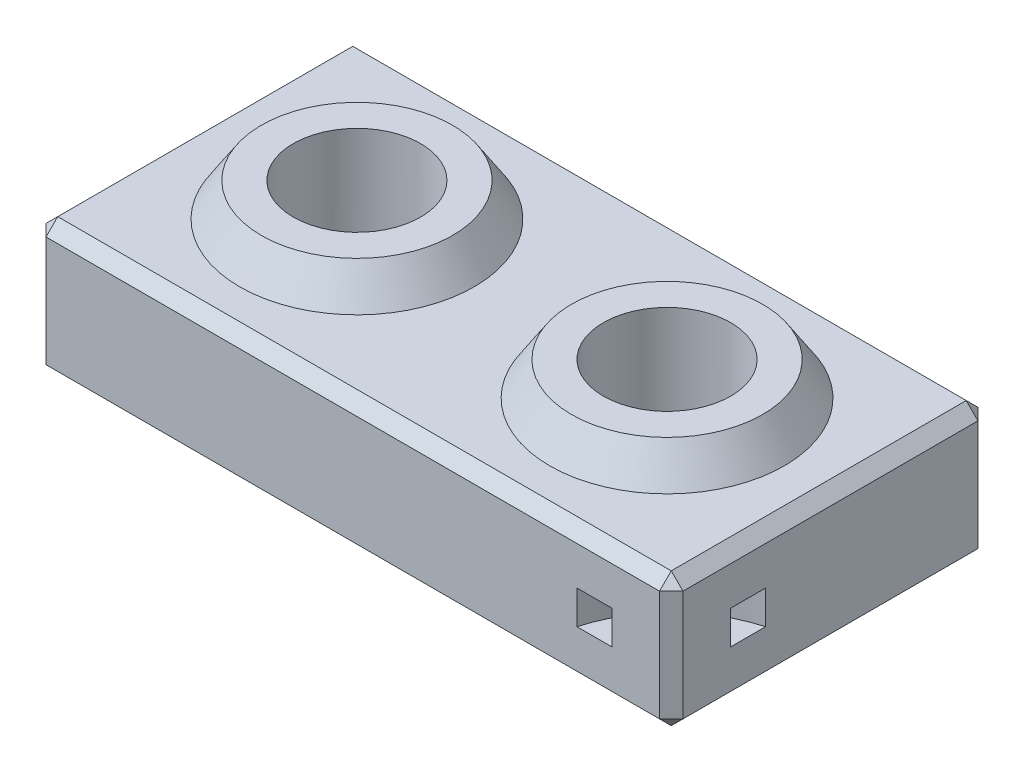
SolidWorks part; units mm, degrees
ref_plane "Alzado" through (0, 0, 0) normal (0, 0, 1) x (1, 0, 0)
ref_plane "Planta" through (0, 0, 0) normal (0, 1, 0) x (1, 0, 0)
ref_plane "Vista lateral" through (0, 0, 0) normal (1, 0, 0) x (0, 0, -1)
sketch "Croquis1" plane through (0, 0, 0) normal (0, 1, 0) x (1, 0, 0)
  line L1 (-19, 9.5) -> (19, 9.5)
  line L2 (-19, 9.5) -> (-19, -9.5)
  line L3 (-19, -9.5) -> (19, -9.5)
  line L4 (19, 9.5) -> (19, -9.5)
  line L5 (-19, 9.5) -> (19, -9.5) construction
  line L6 (-19, -9.5) -> (19, 9.5) construction
  point P0 (0, 0)
  dimension "D1" = 38
  dimension "D2" = 19
extrude "Saliente-Extruir1" add sketch "Croquis1" along normal blind 8
sketch "Croquis2" plane through (0, 8, 0) normal (0, 1, 0) x (1, 0, 0)
  line L0 (-9.25, 0) -> (9.25, 0) construction
  circle A0 centre (-9.25, 0) radius 5
  circle A1 centre (9.25, 0) radius 5
  point P4 (0, 0)
  dimension "D1" = 10
  dimension "D2" = 18.5
extrude "Saliente-Extruir2" add sketch "Croquis2" along normal blind 2
sketch "Croquis3" plane through (0, 10, 0) normal (0, 1, 0) x (1, 0, 0)
  circle A0 centre (9.25, 0) radius 3.8
  circle A1 centre (-9.25, 0) radius 3.8
  circle A2 centre (-9.25, 0) radius 5 construction
  dimension "D1" = 1.2
extrude "Cortar-Extruir1" cut sketch "Croquis3" against normal through all
chamfer "Chaflán2" distance 0.7 angle 45 12 edges at (19, 8, 0) (19, 0, 0) (19, 4, -9.5) (0, 8, -9.5) (0, 0, -9.5) (-19, 4, -9.5) (-19, 8, 0) (-19, 0, 0) (-19, 4, 9.5) (0, 8, 9.5) (19, 4, 9.5) (0, 0, 9.5)
sketch "Croquis4" plane through (0, 0, 0) normal (0, -1, 0) x (1, 0, 0)
  circle A0 centre (9.25, 0) radius 5.25
  circle A1 centre (-9.25, 0) radius 5.25
  dimension "D1" = 10.5
extrude "Cortar-Extruir2" cut sketch "Croquis4" against normal blind 2.2 contours A0 | A1
chamfer "Chaflán1" distance 2 angle 57 4 edges at (9.25, 8, 5) (-9.25, 8, 5) (-9.25, 0, -5.25) (9.25, 0, -5.25) first distance on face at (0, 8, 0) first distance on face at (9.25, 0, -5.25)
sketch "Croquis6" plane through (0, 8, 0) normal (0, 1, 0) x (1, 0, 0)
  line L0 (18.3, -8.8) -> (18.3, -11.7503) construction
  line L1 (18.3, -11.7503) -> (21.2503, -11.7503) construction
  line L2 (21.2503, -11.7503) -> (21.2503, -8.8) construction
  line L3 (21.2503, -8.8) -> (18.3, -8.8) construction
  line L4 (15.8, -8.8) -> (18.3, -6.3) construction
  line L5 (-18.3, -8.8) -> (18.3, -8.8) construction
  line L7 (18.3, -8.8) -> (18.3, 8.8) construction
  line L8 (15.8, -8.8) -> (18.3, -8.8) construction
  line L9 (18.3, -8.8) -> (18.3, -6.3) construction
  line L10 (17.05, -7.55) -> (18.3, -8.8) construction
  circle A0 centre (21.2503, -11.7503) radius 6.1976
  circle A1 centre (21.2503, -11.7503) radius 8.1976
  dimension "D1" = 2
  dimension "D2" = 2.5
extrude "Cortar-Extruir3" cut sketch "Croquis6" against normal blind 2 from offset 3 offset against normal yes
sketch "Croquis7" plane through (0, 8, 0) normal (0, 1, 0) x (1, 0, 0)
  line L0 (-16.25, 0) -> (-18.3, 0) construction
  line L1 (-18.3, 8.8) -> (-18.3, -8.8) construction
  line L2 (-18.3, 0) -> (-18.3, -8.8) construction
  line L3 (-18.3, -8.8) -> (-9.25, -8.8) construction
  line L4 (-18.3, -8.8) -> (18.3, -8.8) construction
  line L5 (-9.25, -8.8) -> (-9.25, -7) construction
  circle A0 centre (-9.25, 0) radius 7 construction
  dimension "D1" = 2.05
  dimension "D2" = 1.8
